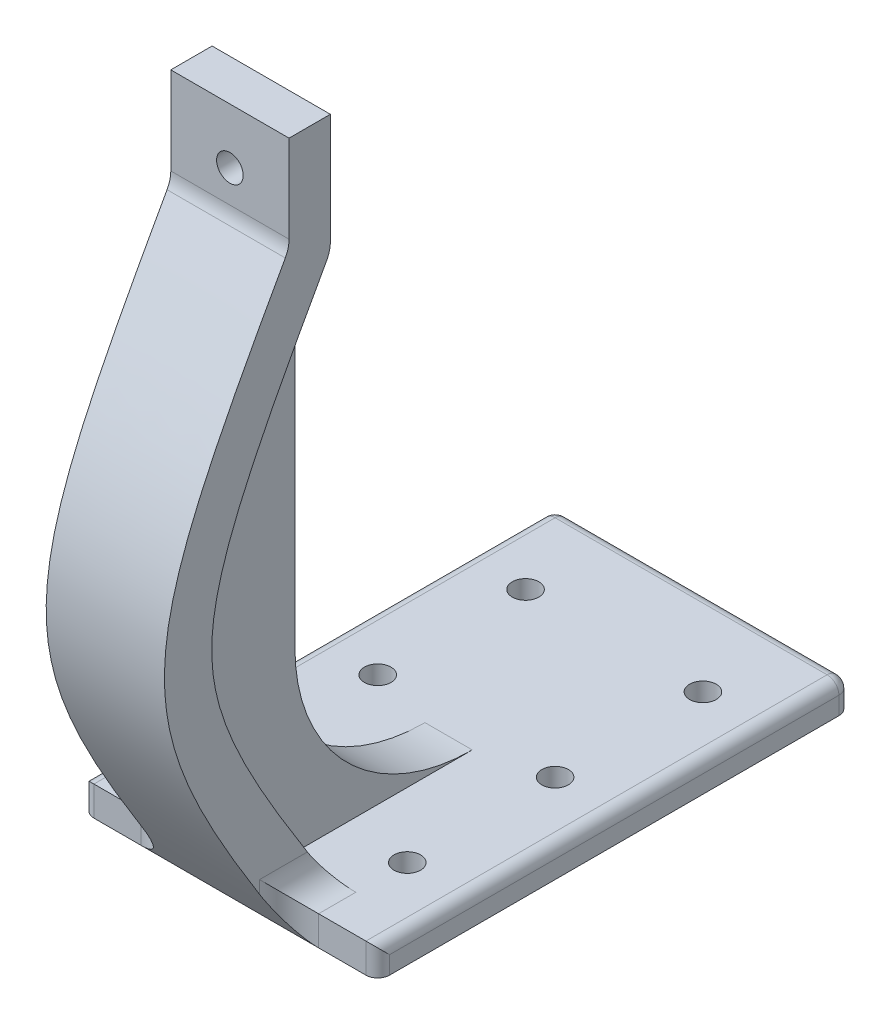
SolidWorks part; units mm, degrees
ref_plane "Front Plane" through (0, 0, 0) normal (0, 0, 1) x (1, 0, 0)
ref_plane "Top Plane" through (0, 0, 0) normal (0, 1, 0) x (1, 0, 0)
ref_plane "Right Plane" through (0, 0, 0) normal (1, 0, 0) x (0, 0, -1)
sketch "Sketch1" plane through (0, 0, 0) normal (0, 1, 0) x (1, 0, 0)
  line L1 (-25, 40) -> (25, 40)
  line L2 (-25, 40) -> (-25, -40)
  line L3 (-25, -40) -> (25, -40)
  line L4 (25, 40) -> (25, -40)
  line L5 (-25, 40) -> (25, -40) construction
  line L6 (-25, -40) -> (25, 40) construction
  point P0 (0, 0)
  dimension "D1" = 50
  dimension "D2" = 80
extrude "Boss-Extrude1" add sketch "Sketch1" along normal blind 5
sketch "Sketch2" plane through (0, 5, 0) normal (0, 1, 0) x (1, 0, 0)
  line L0 (-15, 40) -> (-15, -40) construction
  line L1 (25, 40) -> (-25, 40) construction
  line L2 (-25, -40) -> (25, -40) construction
  line L3 (0, 40) -> (0, -40) construction
  circle A0 centre (-15, 0) radius 2.25
  circle A1 centre (-15, 25) radius 2.25
  circle A2 centre (-15, -25) radius 2.25
  circle A3 centre (15, -25) radius 2.25
  circle A4 centre (15, 0) radius 2.25
  circle A5 centre (15, 25) radius 2.25
  dimension "D1" = 4.5
  dimension "D2" = 4.5
  dimension "D3" = 4.5
  dimension "D4" = 25
  dimension "D5" = 25
  dimension "D6" = 15
extrude "Cut-Extrude1" cut sketch "Sketch2" against normal through all
sketch "Sketch4" plane through (0, 0, 0) normal (1, 0, 0) x (0, 0, -1)
  line L0 (-40, 0) -> (-40, 100) construction
  line L1 (-61.0746, 50.4903) -> (-61.0746, 29.2693) construction
  line L2 (-33.277, 4.336) -> (-33.7052, 5)
  line L3 (-40, 5) -> (40, 5) construction
  line L4 (-40, 0) -> (-33.7052, 5)
  line L5 (-33.0127, 96.1042) -> (-33.0127, 102.4008)
  line L7 (-33.0127, 96.1042) -> (-33.0127, 116.1042)
  line L8 (-33.0127, 116.1042) -> (-40, 116.1042)
  line L9 (-40, 116.1042) -> (-40, 100)
  spline S0 degree 3 poles (-40, 0) (-68.4239, 44.0709) (-67.7731, 50.1873) (-40, 100) knots 0 0 0 0 1 1 1 1
  spline S1 degree 1 poles (-33.277, 4.336) (-33.0127, 96.1042) knots 0 0 1 1 construction
  spline S2 degree 3 poles (-33.277, 4.336) (-33.7112, 5.0092) (-34.5875, 6.3713) (-36.2561, 8.9815) (-38.2375, 12.117) (-40.4305, 15.662) (-43.1134, 20.1232) (-46.0104, 25.226) (-48.7583, 30.6777) (-50.7949, 35.5381) (-52.6145, 41.3643) (-53.4094, 47.7251) (-52.5273, 54.4492) (-50.5892, 60.8734) (-48.4688, 66.3043) (-45.6605, 72.44) (-42.7447, 78.2079) (-40.07, 83.2604) (-37.8952, 87.2788) (-35.9399, 90.8347) (-34.2985, 93.7957) (-33.4386, 95.3404) (-33.0127, 96.1042) knots 0 0 0 0 0.015625 0.03125 0.0625 0.09375 0.125 0.1875 0.25 0.3125 0.375 0.5 0.625 0.6875 0.75 0.8125 0.875 0.90625 0.9375 0.96875 0.984375 1 1 1 1
  point P4 (-61.0746, 47.6165)
  dimension "D1" = 100
  dimension "D3" = 20
  dimension "D2" = 8
extrude "Boss-Extrude2" add sketch "Sketch4" along normal mid plane 20 contours L2 S2 L5 L7 L8 L9 S0 L4 region at (0, 3.4353, 37.5955)
fillet "Fillet1" radius 5 4 edges at (-10, 5, 36.8524) (-10, 2.5, 40) (10, 2.5, 40) (10, 5, 36.8524)
fillet "Fillet2" radius 5 2 edges at (0, 100, 40) (0, 96.1042, 33.0127)
sketch "Sketch5" plane through (0, 0, 33.0127) normal (0, 0, -1) x (-1, 0, 0)
  line L0 (0, 116.1042) -> (0, 97.403) construction
  line L1 (-10, 116.1042) -> (10, 116.1042) construction
  line L2 (-10, 97.403) -> (10, 97.403) construction
  circle A0 centre (0, 106.7536) radius 2.25
  dimension "D1" = 4.5
extrude "Cut-Extrude2" cut sketch "Sketch5" against normal through all
fillet "Fillet3" radius 2 7 edges at (-25, 2.5, 40) (-25, 2.5, -40) (25, 2.5, -40) (25, 2.5, 40) (-25, 5, 0) (0, 5, -40) (25, 5, 0)
sketch "Sketch6" plane through (0, 0, 0) normal (1, 0, 0) x (0, 0, -1)
  line L0 (-33.0127, 97.403) -> (-33.0127, 5)
  line L1 (-40, 5) -> (38, 5) construction
  line L2 (-33.7049, 5) -> (-33.0127, 5)
  arc A0 (-33.6439, 94.9712) -> (-33.0127, 97.403) centre (-38.0127, 97.403) ccw construction
  arc A1 (-33.6439, 94.9712) -> (-33.0127, 97.403) centre (-38.0127, 97.403) ccw
  spline S0 degree 3 poles (2268.1815, -1909.6917) (30.278, -22.6019) (-107.5244, 120.4662) (-14.2881, -25.3829) (33.7897, -95.0443) (-1669.2272, 2519.8088) knots -1.731936 -1.731936 -1.731936 -1.731936 0.96875 0.984375 1.760336 1.760336 1.760336 1.760336 only from (-36.8979, 10) to (-33.7049, 5) construction
  spline S1 degree 3 poles (-2658.8604, 1426.4806) (510.1003, -705.1607) (42.1805, -117.8759) (-40.4305, 15.662) (-43.1134, 20.1232) (-46.0104, 25.226) (-48.7583, 30.6777) (-50.7949, 35.5381) (-52.6145, 41.3643) (-53.4094, 47.7251) (-52.5273, 54.4492) (-50.5892, 60.8734) (-48.4688, 66.3043) (-45.6605, 72.44) (-42.7447, 78.2079) (-40.07, 83.2604) (-37.8952, 87.2788) (-35.9399, 90.8347) (-14.7183, 129.1165) (29.8985, 205.5872) (-1505.5311, -2518.5187) knots -3.406528 -3.406528 -3.406528 -3.406528 0.0625 0.09375 0.125 0.1875 0.25 0.3125 0.375 0.5 0.625 0.6875 0.75 0.8125 0.875 0.90625 0.9375 0.96875 0.984375 1.745545 1.745545 1.745545 1.745545 only from (-36.8979, 10) to (-33.6439, 94.9712) construction
  spline S2 degree 3 poles (-36.8979, 10) (-36.5481, 9.4469) (-35.7887, 8.2504) (-34.7242, 6.5853) (-33.9974, 5.4543) (-33.7049, 5) knots 0.955008 0.955008 0.955008 0.955008 0.96875 0.984375 0.994877 0.994877 0.994877 0.994877
  spline S3 degree 3 poles (-36.8979, 10) (-37.3435, 10.7047) (-38.5589, 12.6366) (-40.4305, 15.662) (-43.1134, 20.1232) (-46.0104, 25.226) (-48.7583, 30.6777) (-50.7949, 35.5381) (-52.6145, 41.3643) (-53.4094, 47.7251) (-52.5273, 54.4492) (-50.5892, 60.8734) (-48.4688, 66.3043) (-45.6605, 72.44) (-42.7447, 78.2079) (-40.07, 83.2604) (-37.8952, 87.2788) (-35.9399, 90.8347) (-34.5008, 93.4307) (-33.8601, 94.5827) (-33.6439, 94.9712) knots 0.044992 0.044992 0.044992 0.044992 0.0625 0.09375 0.125 0.1875 0.25 0.3125 0.375 0.5 0.625 0.6875 0.75 0.8125 0.875 0.90625 0.9375 0.96875 0.984375 0.992297 0.992297 0.992297 0.992297
extrude "Boss-Extrude3" add sketch "Sketch6" along normal mid plane 8
fillet "Fillet4" radius 30 1 edges at (0, 5, 33.0127)
